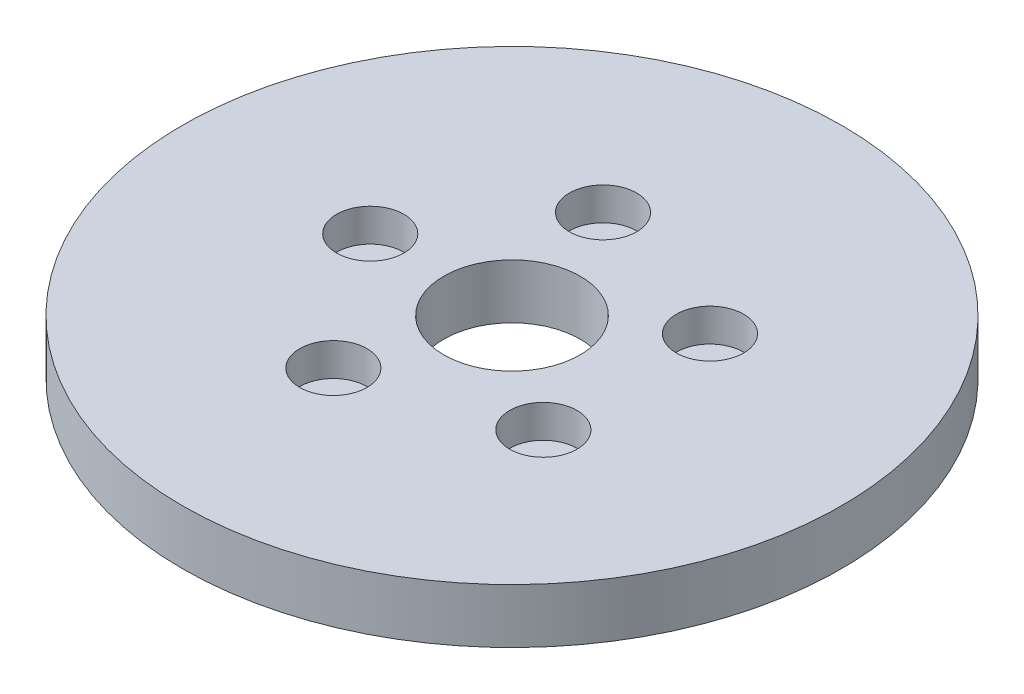
SolidWorks part; units mm, degrees
ref_plane "Front Plane" through (0, 0, 0) normal (0, 0, 1) x (1, 0, 0)
ref_plane "Top Plane" through (0, 0, 0) normal (0, 1, 0) x (1, 0, 0)
ref_plane "Right Plane" through (0, 0, 0) normal (1, 0, 0) x (0, 0, -1)
sketch "Sketch1" plane through (0, 0, 0) normal (0, 1, 0) x (1, 0, 0)
  circle A0 centre (0, 0) radius 72.5
  dimension "FLANGE_OD" = 145
extrude "Boss-Extrude1" add sketch "Sketch1" along normal blind 12
sketch "Sketch2" plane through (0, 0, 0) normal (0, 1, 0) x (1, 0, 0)
  circle A0 centre (0, 0) radius 15
  dimension "BORE_D" = 30
extrude "Cut-Extrude1" cut sketch "Sketch2" along normal through all
sketch "Sketch3" plane through (0, 12, 0) normal (0, 1, 0) x (1, 0, 0)
  circle A0 centre (0, 0) radius 31.1856 construction
  circle A1 centre (-31.1856, 0) radius 7.4025
  dimension "BOLT_D" = 14.8051
  dimension "BOLT_PCD" = 62.3713
extrude "Cut-Extrude2" cut sketch "Sketch3" against normal blind 7.223
pattern_circular "CirPattern1" count 5 over 360 about axis through (0, 0, 0) along (0, 1, 0) of "Cut-Extrude2"
